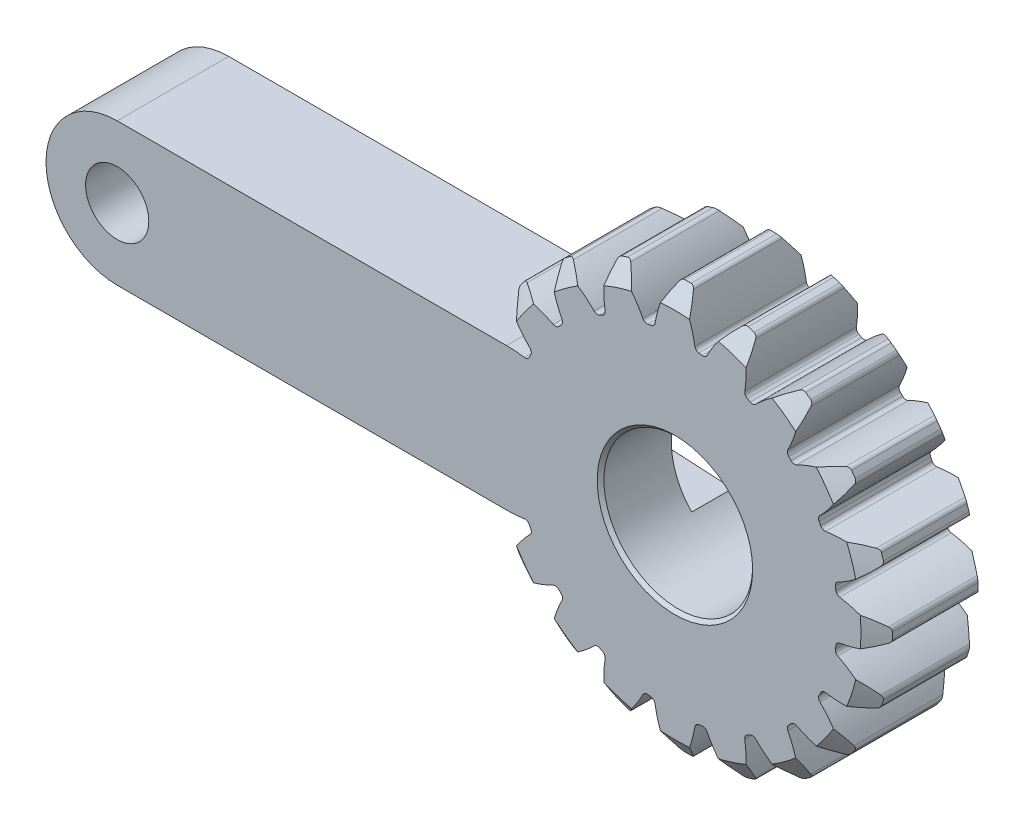
SolidWorks part; units mm, degrees
ref_plane "前视基准面" through (0, 0, 0) normal (0, 0, 1) x (1, 0, 0)
ref_plane "上视基准面" through (0, 0, 0) normal (0, 1, 0) x (1, 0, 0)
ref_plane "右视基准面" through (0, 0, 0) normal (1, 0, 0) x (0, 0, -1)
sketch "草图1" plane through (0, 0, 0) normal (1, 0, 0) x (0, 0, -1)
  line L0 (0, 0) -> (10, 0) construction
  line L1 (0, 4) -> (10, 4)
  line L4 (10, 4) -> (10, 11)
  line L5 (10, 11) -> (0, 11)
  line L6 (0, 11) -> (0, 4)
  line L7 (0, 0) -> (-1, 0) construction
  line L8 (-1, 0) -> (-1, -20) construction
  dimension "P" = 8
  dimension "B" = 10
  dimension "M" = 1
  dimension "Z" = 20
  dimension "D" = 22
sketch "草图2" plane through (0, 0, 0) normal (0, 0, 1) x (1, 0, 0)
  line L0 (0, 4) -> (0, 8) construction
  circle A0 centre (0, 0) radius 4
  circle A3 centre (0, 0) radius 6
  point P6 (0, 6)
  dimension "(D1)" = 4
sketch "草图11" plane through (-11.8785, -4, 0) normal (0, 0, 1) x (1, 0, 0)
  line L0 (11.8785, 4) -> (22.8785, 4) construction
  line L1 (21.8477, 3.2154) -> (11.8785, 4) construction
  circle A0 centre (11.8785, 4) radius 8.75
  arc A1 (20.5595, 2.9033) -> (20.6285, 4) centre (11.8785, 4) ccw construction
  arc A2 (21.8477, 3.2154) -> (21.8785, 4) centre (11.8785, 4) ccw construction
  arc A3 (22.874, 3.6859) -> (22.874, 4.3141) centre (11.8785, 4) ccw construction
  arc A4 (20.5595, 2.9033) -> (22.874, 3.6859) centre (19.7054, 9.2435) ccw construction
  point P1 (31.8785, 4)
  point P7 (11.8785, 5)
  point P13 (21.8477, 3.2154)
  point P17 (22.874, 4.3141)
  point P18 (20.5595, 5.0967)
  dimension "D1" = 22
  dimension "D" = 20
  dimension "D2" = 17.5
  dimension "m" = 1
  dimension "z" = 20
  dimension "D3" = 4.5
  dimension "D4" = 0.6283
  dimension "D5" = 2.1991
extrude "拉伸-齿轮a" add sketch "草图11" against normal blind 6
sketch "草图3" plane through (-1.3611, -4, 0) normal (0, 0, 1) x (1, 0, 0)
  line L1 (1.3611, 4) -> (12.3611, 4) construction
  line L2 (10.1111, 4) -> (12.3611, 4) construction
  circle A2 centre (1.3611, 4) radius 8.75 construction
  arc A3 (10.0421, 2.9033) -> (12.3566, 3.6859) centre (9.188, 9.2435) ccw construction
  arc A4 (12.3566, 3.6859) -> (12.3566, 4.3141) centre (1.3611, 4) ccw construction
  arc A5 (10.0421, 2.9033) -> (10.0421, 5.0967) centre (1.3611, 4) ccw
  arc A6 (10.0421, 2.9033) -> (12.3566, 3.6859) centre (9.188, 9.2435) ccw
  arc A7 (12.3566, 3.6859) -> (12.3566, 4.3141) centre (1.3611, 4) ccw
  arc A8 (10.0421, 5.0967) -> (12.3566, 4.3141) centre (9.188, -1.2435) cw
extrude "拉伸-齿轮b" add sketch "草图3" along normal up to surface (-6 mm away) up to face at (8.75, 0, -6)
fillet "圆角-齿轮" radius 0.25 4 edges at (10.9955, -0.3141, -3) (10.9955, 0.3141, -3) (8.681, -1.0967, -3) (8.681, 1.0967, -3)
pattern_circular "阵列-齿轮" count 20 over 360 about axis through (0, 0, -6) along (0, 0, 1) of "拉伸-齿轮b", "圆角-齿轮"
sketch "草图4" plane through (0, 0, -6) normal (0, 0, -1) x (-1, 0, 0)
  line L0 (-10, 0) -> (-12, 0) construction
  circle A0 centre (0, 0) radius 12
  circle A1 centre (0, 0) radius 10
extrude "切除-齿轮" cut sketch "草图4" against normal blind 1 draft 55
extrude "切除-拉伸2" cut sketch "草图4<2>" along normal blind 1 draft 55 from vertex starting at point (0, 4, 0)
sketch "草图4<2>" plane through (0, 0, -6) normal (0, 0, -1) x (-1, 0, 0) same geometry as "草图4"
sketch "草图13" plane through (0, 0, 0) normal (0, 0, 1) x (1, 0, 0)
  circle A0 centre (0, 0) radius 4
extrude "切除-拉伸4" cut sketch "草图13" against normal through all
chamfer "倒角1" distance 0.18 angle 45 2 edges at (4, 0, -6) (4, 0, 0)
sketch "草图14" plane through (0, 0, 0) normal (1, 0, 0) x (0, 0, -1)
  line L0 (0, 0) -> (10, 0) construction
  line L1 (0, 6) -> (0, -6) construction
  line L2 (12.5, 6.05) -> (7.5, 6.05)
  line L3 (12.5, 6.05) -> (12.5, 6)
  line L4 (12.5, 6) -> (7.5, 6)
  line L5 (7.5, 6.05) -> (7.5, 6)
  line L6 (2.5, 6.05) -> (-2.5, 6.05)
  line L7 (2.5, 6.05) -> (2.5, 6)
  line L8 (2.5, 6) -> (-2.5, 6)
  line L9 (-2.5, 6.05) -> (-2.5, 6)
  line L10 (10, 4) -> (10, 11) construction
  line L11 (7.5, 6) -> (2.5, 6) construction
  point P12 (0, 6)
  point P16 (10, 6)
  dimension "D1" = 0.05
sketch "草图15" plane through (0, 0, 0) normal (0, 0, 1) x (1, 0, 0)
  line L0 (-9.0642, -3.8292) -> (-30, -3.8292)
  line L1 (-9.0642, 3.8292) -> (-4.6582, 0.5892)
  line L2 (-30, 3.8292) -> (-9.0642, 3.8292)
  line L3 (-4.6582, 0.5892) -> (-9.0642, -3.8292)
  arc A0 (-9.2388, -3.8268) -> (-8.0985, -3.7559) centre (-9.0642, 2.5682) ccw construction
  arc A1 (-8.0985, 3.7559) -> (-9.2388, 3.8268) centre (-9.0642, -2.5682) ccw construction
  arc A2 (-9.2388, 3.8268) -> (-10.2166, 3.7246) centre (-9.0642, -2.5682) ccw construction
  arc A3 (-30, 3.8292) -> (-30, -3.8292) centre (-30, 0) ccw
  circle A4 centre (-30, 0) radius 1.7
  dimension "D2" = 3.4
  dimension "D1" = 30
extrude "凸台-拉伸1" add sketch "草图15" against normal up to surface (6 mm away) up to face at (4.18, 0, -6)
sketch "草图16" plane through (0, 0, -6) normal (0, 0, -1) x (-1, 0, 0)
  line L0 (0, 0) -> (15, 0) construction
  line L1 (15.1122, 2.097) -> (2.9047, 2.75)
  line L2 (15.1122, -2.097) -> (2.9047, -2.75)
  circle A0 centre (15, 0) radius 2.1
  circle A3 centre (0, 0) radius 4
  dimension "D2" = 4.2
  dimension "D4" = 8
  dimension "D1" = 15
  dimension "D3" = 5.5
extrude "切除-拉伸5" cut sketch "草图16" against normal blind 2.2 contours L0 A3 L2 A0 | A3 L0 A0 L1 | A0 region at (-8.3584, 1.2829, -6) region at (-8.3584, -1.2829, -6) region at (-13.5961, 1.481, -6)
